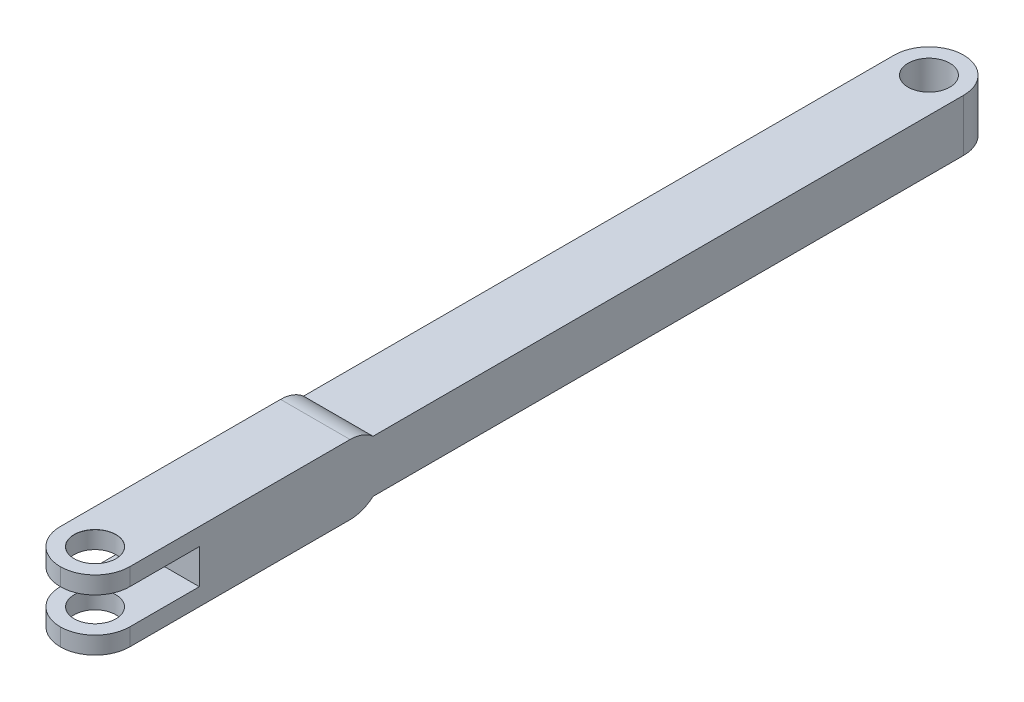
SolidWorks part; units mm, degrees
ref_plane "Plan de face" through (0, 0, 0) normal (0, 0, 1) x (1, 0, 0)
ref_plane "Plan de dessus" through (0, 0, 0) normal (0, 1, 0) x (1, 0, 0)
ref_plane "Plan de droite" through (0, 0, 0) normal (1, 0, 0) x (0, 0, -1)
sketch "Esquisse1" plane through (0, 0, 0) normal (1, 0, 0) x (0, 0, -1)
  line L0 (70, 10) -> (-10, 10)
  line L1 (-10, 10) -> (-10, 5)
  line L2 (70, 10) -> (70, 7.5)
  line L3 (70, 7.5) -> (250, 7.5)
  line L4 (-10, 5) -> (20, 5)
  line L5 (20, 5) -> (20, -5)
  line L6 (250, 7.5) -> (250, -7.5)
  line L7 (11, 0) -> (-11, 0) construction
  line L8 (-10, -5) -> (20, -5)
  line L9 (70, -7.5) -> (250, -7.5)
  line L10 (70, -10) -> (70, -7.5)
  line L11 (-10, -10) -> (-10, -5)
  line L12 (70, -10) -> (-10, -10)
  point P12 (250, 0)
  point P13 (20, 0)
  dimension "10" = 10
  dimension "D2" = 15
  dimension "D3" = 5
  dimension "D4" = 50
  dimension "D5" = 30
  dimension "D6" = 20
  dimension "D7" = 180
extrude "Boss.-Extru.1" add sketch "Esquisse1" along normal mid plane 20
fillet "Congé1" radius 10 8 edges at (0, -10, -70) (0, 10, -70) (-10, -7.5, 10) (-10, 7.5, 10) (10, -7.5, 10) (10, 7.5, 10) (-10, 0, -250) (10, 0, -250)
sketch "Esquisse4" plane through (0, 10, 0) normal (0, 1, 0) x (1, 0, 0)
  line L0 (10, 240) -> (-10, 240) construction
  line L1 (0, 250) -> (0, 217.7488) construction
  point P0 (0, 0)
  point P9 (0, 240)
hole_wizard "Dégagement M102" positions "Esquisse4" profile "Esquisse5" hole size "M10" standard "ISO" end condition through all
sketch "Esquisse5" plane through (0, 10, 0) normal (1, 0, 0) x (0, 0, 1)
  line L0 (0, 0) -> (0, 20)
  line L1 (0, 20) -> (6, 20)
  line L2 (6, 20) -> (6, 0.025)
  line L3 (6, 0.025) -> (6.025, 0)
  line L5 (6.025, 0) -> (0, 0)
  line L6 (-6, 0.025) -> (-6.025, 0) construction
  line L11 (0, -6.35) -> (0, 107.95) construction
  dimension "Diamètre du perçage jusqu'au prochain" = 12
  dimension "Profondeur du perçage jusqu'au prochain" = 20
  dimension "Diamètre du fraisage entrant" = 12.05
  dimension "Angle du fraisage entrant" = 90
